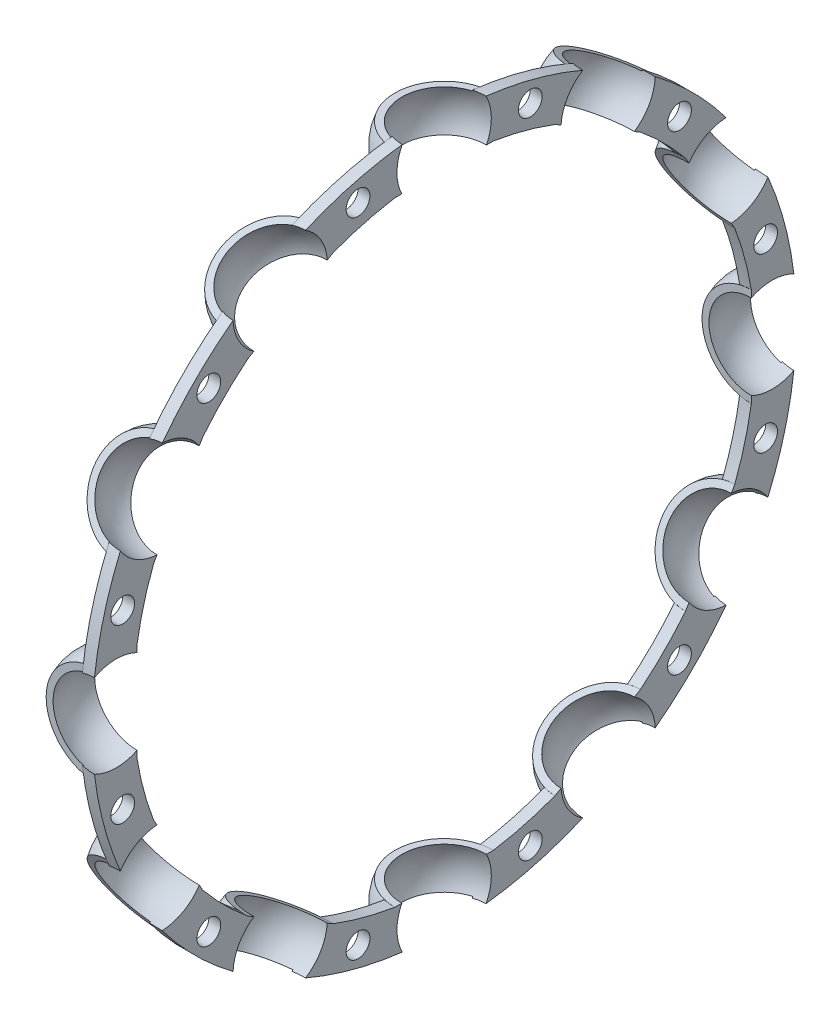
SolidWorks part; units mm, degrees
ref_plane "Front Plane" through (0, 0, 0) normal (0, 0, 1) x (1, 0, 0)
ref_plane "Top Plane" through (0, 0, 0) normal (0, 1, 0) x (1, 0, 0)
ref_plane "Right Plane" through (0, 0, 0) normal (1, 0, 0) x (0, 0, -1)
sketch "Sketch4" plane through (0, 0, 0) normal (0, 0, 1) x (1, 0, 0)
  line L0 (-4.5, 0) -> (-3.9688, 0) construction
  line L1 (-4.1458, 1.75) -> (-3.5621, 1.75)
  line L2 (-4.1458, -1.75) -> (-3.5621, -1.75)
  line L4 (0, -4.4143) -> (0, 6.4726) construction
  arc A0 (-4.1458, 1.75) -> (-4.1458, -1.75) centre (0, 0) ccw
  arc A1 (-3.5621, 1.75) -> (-3.5621, -1.75) centre (0, 0) ccw
  dimension "D1" = 9
  dimension "D2" = 7.9375
  dimension "D3" = 3.5
revolve "Revolve2" add sketch "Sketch4" angle 180 mid plane about L4
sketch "Sketch5" plane through (0, 0, 0) normal (1, 0, 0) x (0, 0, -1)
  circle A0 centre (0, -27.59) radius 27.59 construction
  circle A1 centre (0, -27.59) radius 29.6315
  circle A2 centre (0, -27.59) radius 26.1705
  dimension "D1" = 55.18
ref_axis "Axis1" through (-11.056, -27.59, 0) along (1, 0, 0)
extrude "Boss-Extrude1" add sketch "Sketch5" against normal blind 1
pattern_circular "CirPattern1" count 12 over 360 about axis through (-11.056, -27.59, 0) along (1, 0, 0) of "Revolve2"
sketch "Sketch6" plane through (0, 0, 0) normal (0, 0, 1) x (1, 0, 0)
  line L0 (0, 3.9688) -> (0, -3.9688)
  arc A2 (0, 3.9688) -> (0, -3.9688) centre (0, 0) ccw
  dimension "D1" = 7.9375
revolve "Cut-Revolve1" cut sketch "Sketch6" angle 360 about L0
pattern_circular "CirPattern2" count 12 over 360 about axis through (-11.056, -27.59, 0) along (1, 0, 0) of "Cut-Revolve1"
sketch "Sketch7" plane through (-1, 0, 0) normal (-1, 0, 0) x (0, 0, 1)
  line L0 (-27.0459, -20.3431) -> (0, -27.59) construction
  line L1 (0, -27.59) -> (-29.34, -27.59) construction
  line L2 (-29.34, -23.5666) -> (-29.34, -31.6134) construction
  circle A0 centre (-27.0459, -20.3431) radius 1
  point P0 (-27.0459, -20.3431)
  point P3 (0, -27.59)
  dimension "D2" = 2
  dimension "D1" = 28
  dimension "D3" = 15
extrude "Cut-Extrude1" cut sketch "Sketch7" against normal through all
pattern_circular "CirPattern3" count 12 over 360 about axis through (-11.056, -27.59, 0) along (1, 0, 0) of "Cut-Extrude1"
